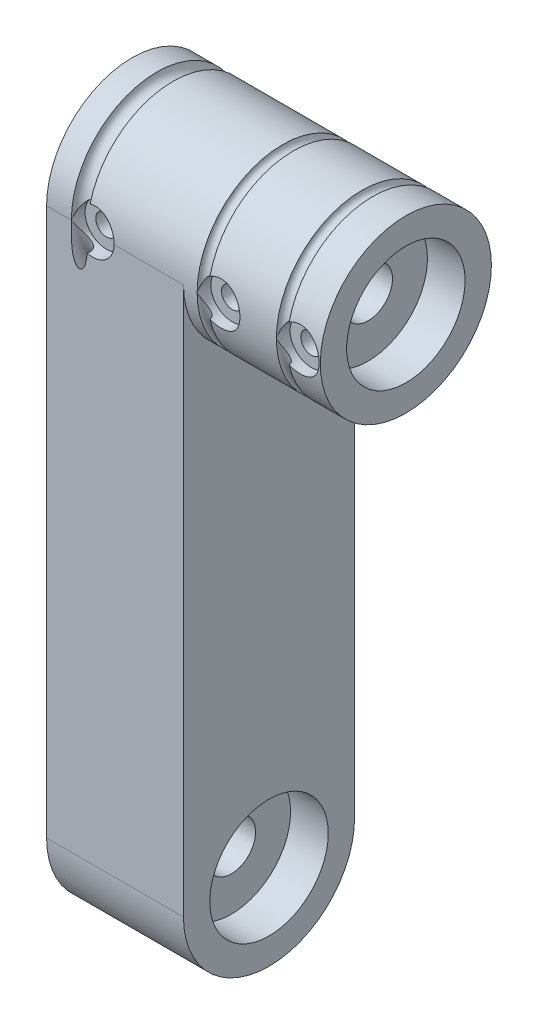
SolidWorks part; units mm, degrees
other "Markup2"
sketch "Sketch8" plane through (0, -66.675, 15.875) normal (-0.2611, -0.7459, 0.6127) x (0.965, -0.1848, 0.1862)
sketch "Sketch10" plane through (0, -66.675, 15.875) normal (-0.2611, -0.7459, 0.6127) x (0.965, -0.1848, 0.1862)
sketch "Sketch17" plane through (0, -66.675, 15.875) normal (-0.2611, -0.7459, 0.6127) x (0.965, -0.1848, 0.1862)
other "Markup3"
sketch "Sketch9" plane through (44.45, -66.675, 15.875) normal (0.0765, -0.4628, 0.8831) x (0.9939, -0.035, -0.1045)
sketch "Sketch11" plane through (50.8, -66.675, 15.875) normal (0.0765, -0.4628, 0.8831) x (0.9939, -0.035, -0.1045)
sketch "Sketch18" plane through (50.8, -66.675, 15.875) normal (0.0765, -0.4628, 0.8831) x (0.9939, -0.035, -0.1045)
ref_plane "Front Plane" through (0, 0, 0) normal (0, 0, 1) x (1, 0, 0)
ref_plane "Top Plane" through (0, 0, 0) normal (0, 1, 0) x (1, 0, 0)
ref_plane "Right Plane" through (0, 0, 0) normal (1, 0, 0) x (0, 0, -1)
sketch "Sketch1" plane through (0, 0, 0) normal (1, 0, 0) x (0, 0, -1)
  line L2 (15.875, 50.8) -> (15.875, -50.8)
  line L4 (-15.875, 50.8) -> (-15.875, -50.8)
  line L5 (15.875, 50.8) -> (-15.875, -50.8) construction
  line L6 (15.875, -50.8) -> (-15.875, 50.8) construction
  arc A0 (-15.875, 50.8) -> (15.875, 50.8) centre (0, 50.8) cw
  arc A1 (-15.875, -50.8) -> (15.875, -50.8) centre (0, -50.8) ccw
  circle A3 centre (0, -50.8) radius 4.5
  circle A4 centre (0, 50.8) radius 4.5
  point P0 (0, 0)
  point P14 (0, 50.8)
  dimension "D3" = 9
  dimension "D1" = 101.6
  dimension "D2" = 31.75
extrude "Boss-Extrude1" add sketch "Sketch1" along normal blind 25.4
sketch "Sketch2" plane through (25.4, 0, 0) normal (1, 0, 0) x (0, 0, -1)
  circle A0 centre (0, 50.8) radius 15.875
  arc A1 (15.875, 50.8) -> (-15.875, 50.8) centre (0, 50.8) ccw construction
  circle A2 centre (0, 50.8) radius 4.5
  circle A3 centre (0, 50.8) radius 4.5 construction
extrude "Boss-Extrude2" add sketch "Sketch2" along normal blind 25.4
sketch "Sketch3" plane through (0, 0, 0) normal (0, 0, 1) x (1, 0, 0)
  line L0 (27.94, 66.675) -> (29.94, 66.675)
  line L1 (50.8, 66.675) -> (0, 66.675) construction
  line L2 (42.64, 66.675) -> (44.64, 66.675)
  line L3 (25.4, 34.925) -> (25.4, 50.8) construction
  line L4 (45.6613, 34.925) -> (45.6613, 66.675) construction
  line L5 (25.4, 34.925) -> (50.8, 34.925) construction
  line L6 (45.6613, 50.8) -> (25.4, 50.8) construction
  arc A0 (27.94, 66.675) -> (29.94, 66.675) centre (28.94, 66.675) ccw
  arc A1 (42.64, 66.675) -> (44.64, 66.675) centre (43.64, 66.675) ccw
  dimension "D1" = 2
  dimension "D2" = 2.54
  dimension "D3" = 12.7
revolve "Cut-Revolve1" cut sketch "Sketch3" angle 360 about L6
sketch "Sketch5" plane through (0, 0, 15.875) normal (0, 0, 1) x (1, 0, 0)
  line L0 (48.6662, 66.675) -> (48.6662, 34.925) construction
  line L3 (48.6662, 50.8) -> (38.9914, 50.8) construction
  line L5 (27.94, 66.675) -> (29.94, 66.675) construction
  line L6 (42.64, 66.675) -> (44.64, 66.675) construction
  line L7 (42.64, 66.675) -> (42.64, 34.925) construction
  line L8 (27.94, 66.675) -> (27.94, 34.925) construction
  line L9 (50.8, 66.675) -> (44.64, 66.675) construction
  arc A0 (42.64, 66.675) -> (44.64, 66.675) centre (43.64, 66.675) ccw construction
  circle A1 centre (31.9088, 50.8) radius 3.9687
  circle A2 centre (46.6088, 50.8) radius 3.9687
  dimension "D1" = 7.9375
extrude "Cut-Extrude1" cut sketch "Sketch5" against normal blind 6.35
sketch "Sketch7" plane through (0, 0, 9.525) normal (0, 0, 1) x (1, 0, 0)
  circle A0 centre (31.9088, 50.8) radius 1.9844
  circle A1 centre (31.9088, 50.8) radius 3.9687
  circle A2 centre (31.9088, 50.8) radius 3.9688 construction
  circle A3 centre (46.6088, 50.8) radius 1.9844
  circle A4 centre (46.6088, 50.8) radius 3.9687
  arc A5 (44.64, 47.354) -> (44.64, 54.246) centre (46.6088, 50.8) ccw construction
  dimension "D1" = 3.9688
extrude "Boss-Extrude3" add sketch "Sketch7" along normal blind 3.81 contours A1 | A0 | A4 | A3
sketch "Sketch14" plane through (25.4, 0, 0) normal (1, 0, 0) x (0, 0, -1)
  circle A0 centre (0, -50.8) radius 10.9919
  dimension "D1" = 21.9837
extrude "Cut-Extrude4" cut sketch "Sketch14" against normal blind 6.985
sketch "Sketch16" plane through (50.8, 0, 0) normal (1, 0, 0) x (0, 0, -1)
  circle A0 centre (0, 50.8) radius 10.9919
  dimension "D1" = 21.9837
extrude "Cut-Extrude5" cut sketch "Sketch16" against normal blind 6.985
sketch "Sketch19" plane through (0, 0, 0) normal (0, 0, 1) x (1, 0, 0)
  line L0 (4.596, 66.675) -> (7.596, 66.675) construction
  line L1 (27.94, 66.675) -> (0, 66.675) construction
  line L2 (0, 66.675) -> (0, 50.8) construction
  line L3 (0, 50.8) -> (25.4, 50.8) construction
  circle A0 centre (6.096, 66.675) radius 1.5
  dimension "D1" = 3
  dimension "D2" = 6.096
revolve "Cut-Revolve2" cut sketch "Sketch19" angle 360 about L3
sketch "Sketch20" plane through (0, 0, 15.875) normal (0, 0, 1) x (1, 0, 0)
  line L0 (4.596, 50.8) -> (4.596, 66.675) construction
  line L1 (31.9088, 50.8) -> (46.6088, 50.8) construction
  circle A0 centre (8.5648, 50.8) radius 3.9688
  arc A1 (29.94, 47.354) -> (29.94, 54.246) centre (31.9088, 50.8) ccw construction
  point P4 (0, 0)
extrude "Cut-Extrude6" cut sketch "Sketch20" against normal blind 6.35
sketch "Sketch21" plane through (0, 0, 9.525) normal (0, 0, 1) x (1, 0, 0)
  circle A0 centre (8.5648, 50.8) radius 1.9844
  circle A1 centre (8.5648, 50.8) radius 3.9687
  circle A2 centre (8.5648, 50.8) radius 3.9688 construction
  arc A3 (12.5335, 50.8) -> (7.596, 54.6487) centre (8.5648, 50.8) ccw construction
  dimension "D1" = 3.9688
extrude "Boss-Extrude4" add sketch "Sketch21" along normal blind 3.81
sketch "Sketch12" plane through (0, 0, 0) normal (-1, 0, 0) x (0, 0, 1)
  circle A0 centre (0, 50.8) radius 10.9919
  circle A1 centre (0, -50.8) radius 10.9919
  dimension "D1" = 21.9837
extrude "Cut-Extrude2" cut sketch "Sketch12" against normal blind 6.985
sketch "Sketch22" plane through (0, 0, 0) normal (0, 0, 1) x (1, 0, 0)
  line L0 (4.596, 66.675) -> (7.596, 66.675) construction
  line L1 (7.596, 66.675) -> (6.096, 66.675) construction
  line L2 (6.096, 66.675) -> (6.096, 65.175) construction
  arc A0 (4.596, 66.675) -> (7.596, 66.675) centre (6.096, 66.675) ccw construction
  point P10 (6.096, 66.675)
